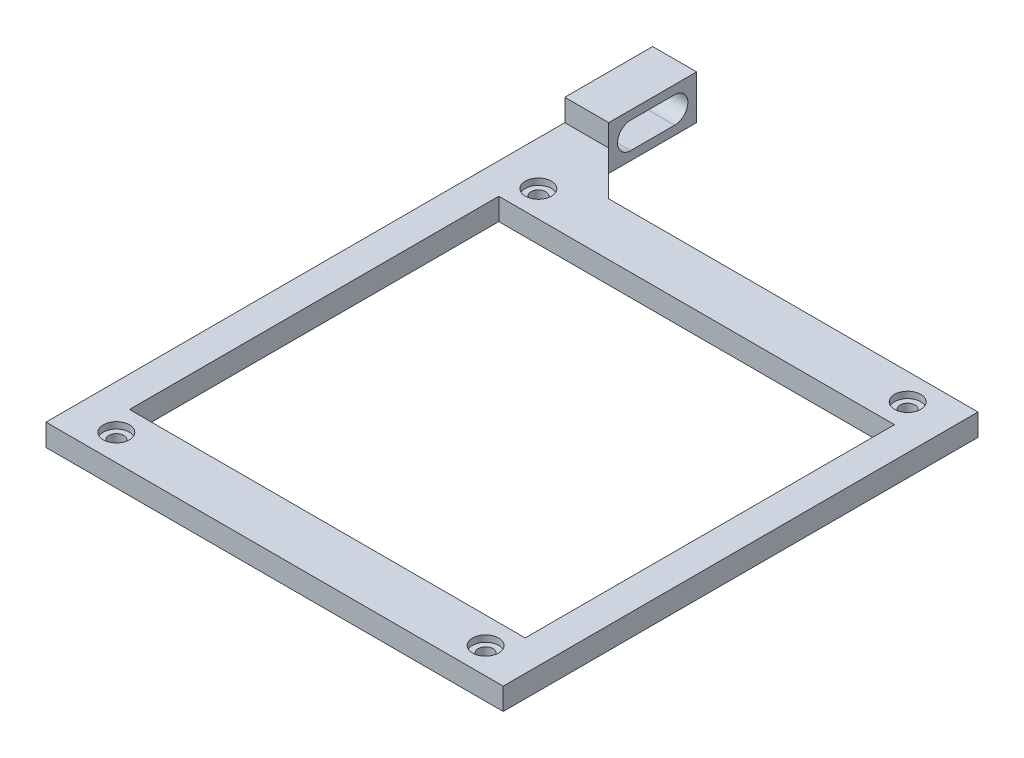
SolidWorks part; units mm, degrees
ref_plane "Front Plane" through (0, 0, 0) normal (0, 0, 1) x (1, 0, 0)
ref_plane "Top Plane" through (0, 0, 0) normal (0, 1, 0) x (1, 0, 0)
ref_plane "Right Plane" through (0, 0, 0) normal (1, 0, 0) x (0, 0, -1)
sketch "Sketch1" plane through (0, 0, 0) normal (0, 1, 0) x (1, 0, 0)
  line L1 (0, 0) -> (132.08, 0)
  line L2 (0, 0) -> (0, 137.16)
  line L3 (0, 137.16) -> (132.08, 137.16)
  line L4 (132.08, 0) -> (132.08, 137.16)
  dimension "D1" = 132.08
  dimension "D2" = 137.16
extrude "Boss-Extrude1" add sketch "Sketch1" along normal blind 6.35
ref_axis "Axis1" through (66.04, 6.35, 0) along (0, 0, -1)
ref_axis "Axis2" through (0, 6.35, -68.58) along (1, 0, 0)
hole_wizard "CBORE for #6 Button Head Cap Screw1" positions "Sketch4" profile "Sketch3" counterbore size "#6" standard "ANSI Inch" end condition up to next
sketch "Sketch4" plane through (0, 6.35, 0) normal (0, 1, 0) x (1, 0, 0)
  line L0 (12.7, 129.54) -> (119.38, 129.54)
  line L1 (119.38, 129.54) -> (119.38, 7.62)
  line L2 (119.38, 7.62) -> (12.7, 7.62)
  line L4 (12.7, 129.54) -> (12.7, 7.62)
  line L7 (66.04, 0) -> (66.04, 137.16) construction
  line L8 (0, 68.58) -> (132.08, 68.58) construction
  point P0 (12.7, 129.54)
  point P2 (119.38, 129.54)
  point P4 (119.38, 7.62)
  point P6 (12.7, 7.62)
  point P28 (66.04, 129.54)
  point P31 (119.38, 68.58)
  dimension "D1" = 106.68
  dimension "D2" = 121.92
sketch "Sketch3" plane through (12.7, 6.35, -129.54) normal (1, 0, 0) x (0, 0, 1)
  line L0 (0, 0) -> (0, 6.35)
  line L1 (0, 6.35) -> (2.1526, 6.35)
  line L3 (2.1526, 6.35) -> (2.1527, 1.8542)
  line L4 (2.1527, 1.8542) -> (3.7706, 1.8542)
  line L5 (3.7706, 1.8542) -> (3.7706, 0)
  line L7 (3.7706, 0) -> (0, 0)
  line L11 (0, -6.35) -> (0, 107.95) construction
  dimension "Thru Hole Dia." = 4.3053
  dimension "Thru Hole Depth" = 6.35
  dimension "C'Bore Dia." = 7.5413
  dimension "C'Bore Depth" = 1.8542
sketch "Sketch5" plane through (0, 6.35, 0) normal (0, 1, 0) x (1, 0, 0)
  line L0 (0, 68.58) -> (132.08, 68.58) construction
  line L1 (8.89, 15.24) -> (123.19, 15.24)
  line L2 (8.89, 15.24) -> (8.89, 121.92)
  line L3 (8.89, 121.92) -> (123.19, 121.92)
  line L4 (123.19, 15.24) -> (123.19, 121.92)
  line L5 (8.89, 15.24) -> (123.19, 121.92) construction
  line L6 (8.89, 121.92) -> (123.19, 15.24) construction
  line L7 (66.04, 0) -> (66.04, 137.16) construction
  point P0 (66.04, 68.58)
  dimension "D1" = 114.3
  dimension "D2" = 106.68
extrude "Cut-Extrude1" cut sketch "Sketch5" against normal through all
sketch "Sketch6" plane through (0, 0, 0) normal (0, -1, 0) x (-1, 0, 0)
  line L1 (0, 137.16) -> (-12.7, 137.16)
  line L2 (0, 137.16) -> (0, 175.26)
  line L3 (0, 175.26) -> (-12.7, 175.26)
  line L4 (-12.7, 137.16) -> (-12.7, 175.26)
  dimension "D1" = 12.7
  dimension "D2" = 38.1
extrude "Boss-Extrude2" add sketch "Sketch6" against normal blind 6.35
sketch "Sketch7" plane through (0, 0, -175.26) normal (0, 0, -1) x (-1, 0, 0)
  line L4 (0, 6.35) -> (-12.7, 6.35)
  line L5 (0, 6.35) -> (0, 12.7)
  line L6 (0, 12.7) -> (-12.7, 12.7)
  line L7 (-12.7, 6.35) -> (-12.7, 12.7)
  point P6 (0, 0)
  dimension "D1" = 6.35
extrude "Boss-Extrude3" add sketch "Sketch7" against normal blind 25.4
sketch "Sketch8" plane through (0, 0, 0) normal (-1, 0, 0) x (0, 0, 1)
  line L0 (-175.26, 6.35) -> (-149.86, 6.35)
  line L1 (-175.26, 12.7) -> (-175.26, 0) construction
  line L3 (-168.91, 6.35) -> (-156.21, 6.35) construction
  line L4 (-168.91, 10.16) -> (-156.21, 10.16)
  line L5 (-168.91, 2.54) -> (-156.21, 2.54)
  arc A0 (-168.91, 10.16) -> (-168.91, 2.54) centre (-168.91, 6.35) ccw
  arc A1 (-156.21, 2.54) -> (-156.21, 10.16) centre (-156.21, 6.35) ccw
  point P4 (0, 0)
  point P8 (-162.56, 6.35)
  dimension "D1" = 3.81
  dimension "D2" = 6.35
extrude "Cut-Extrude2" cut sketch "Sketch8" against normal up to next contours L5 A1 L0 A0 | L0 A1 L4 A0 region at (0, 8.1628, -162.56) region at (0, 4.5372, -162.56)
ref_axis "Axis3" through (12.7, 6.35, -162.56) along (-1, 0, 0)
ref_axis "Axis4" through (12.7, 6.35, -156.21) along (-1, 0, 0)
chamfer "Chamfer1" distance 12.7 angle 45 1 edges at (12.7, 3.175, -137.16)
